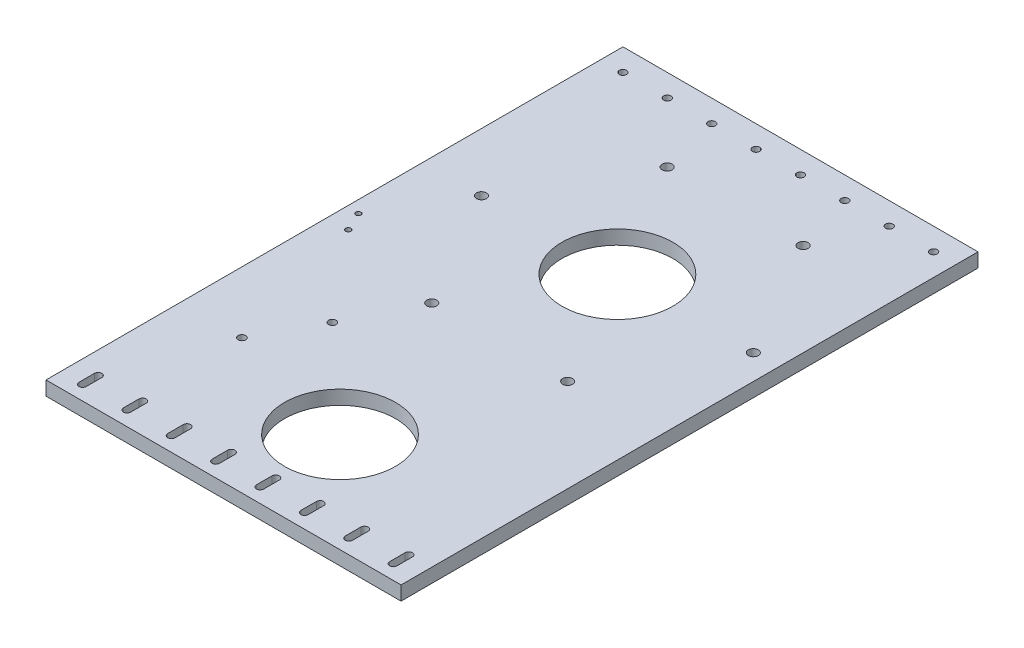
SolidWorks part; units mm, degrees
material "6061 Alloy"
ref_plane "Front Plane" through (0, 0, 0) normal (0, 0, 1) x (1, 0, 0)
ref_plane "Top Plane" through (0, 0, 0) normal (0, 1, 0) x (1, 0, 0)
ref_plane "Right Plane" through (0, 0, 0) normal (1, 0, 0) x (0, 0, -1)
sketch "Sketch1" plane through (0, 0, 0) normal (0, 1, 0) x (1, 0, 0)
  line L0 (87.5, 260) -> (87.5, 0) construction
  line L1 (0, 0) -> (160, 0)
  line L2 (0, 0) -> (0, 260)
  line L3 (0, 260) -> (160, 260)
  line L4 (160, 0) -> (160, 260)
  line L5 (87.5, 170) -> (148.75, 170) construction
  line L6 (10, 6.5) -> (10, 13.5) construction
  line L7 (5.4755, 135.2989) -> (9.5163, 126.7011) construction
  line L8 (22, 0) -> (22, 260) construction
  line L9 (22, 136) -> (0, 136) construction
  line L10 (22, 126) -> (0, 126) construction
  line L11 (0, 136) -> (0, 126) construction
  line L12 (17.3003, 136) -> (22, 126) construction
  line L13 (8.35, 6.5) -> (8.35, 13.5)
  line L14 (11.65, 6.5) -> (11.65, 13.5)
  line L15 (10, 250) -> (10, 0) construction
  line L16 (31.65, 6.5) -> (31.65, 13.5)
  line L17 (28.35, 6.5) -> (28.35, 13.5)
  line L18 (30, 6.5) -> (30, 13.5) construction
  line L19 (51.65, 6.5) -> (51.65, 13.5)
  line L20 (48.35, 6.5) -> (48.35, 13.5)
  line L21 (50, 6.5) -> (50, 13.5) construction
  line L22 (71.65, 6.5) -> (71.65, 13.5)
  line L23 (68.35, 6.5) -> (68.35, 13.5)
  line L24 (70, 6.5) -> (70, 13.5) construction
  line L25 (91.65, 6.5) -> (91.65, 13.5)
  line L26 (88.35, 6.5) -> (88.35, 13.5)
  line L27 (90, 6.5) -> (90, 13.5) construction
  line L28 (111.65, 6.5) -> (111.65, 13.5)
  line L29 (108.35, 6.5) -> (108.35, 13.5)
  line L30 (110, 6.5) -> (110, 13.5) construction
  line L31 (131.65, 6.5) -> (131.65, 13.5)
  line L32 (128.35, 6.5) -> (128.35, 13.5)
  line L33 (130, 6.5) -> (130, 13.5) construction
  line L34 (151.65, 6.5) -> (151.65, 13.5)
  line L35 (148.35, 6.5) -> (148.35, 13.5)
  line L36 (150, 6.5) -> (150, 13.5) construction
  line L37 (10, 250) -> (30, 250) construction
  circle A0 centre (87.5, 170) radius 25
  circle A1 centre (87.5, 45) radius 25
  circle A2 centre (87.5, 170) radius 61.25 construction
  circle A3 centre (148.75, 170) radius 2.25
  circle A4 centre (118.125, 116.9559) radius 2.25
  circle A5 centre (56.875, 116.9559) radius 2.25
  circle A6 centre (26.25, 170) radius 2.25
  circle A7 centre (56.875, 223.0441) radius 2.25
  circle A8 centre (118.125, 223.0441) radius 2.25
  circle A10 centre (5.4755, 135.2989) radius 1.175
  circle A11 centre (9.5163, 126.7011) radius 1.175
  circle A12 centre (87.5, 170) radius 78 construction
  circle A13 centre (10, 250) radius 1.65
  arc A14 (8.35, 6.5) -> (11.65, 6.5) centre (10, 6.5) ccw
  arc A15 (11.65, 13.5) -> (8.35, 13.5) centre (10, 13.5) ccw
  circle A16 centre (30, 250) radius 1.65
  arc A17 (28.35, 6.5) -> (31.65, 6.5) centre (30, 6.5) ccw
  arc A18 (31.65, 13.5) -> (28.35, 13.5) centre (30, 13.5) ccw
  circle A19 centre (50, 250) radius 1.65
  arc A20 (48.35, 6.5) -> (51.65, 6.5) centre (50, 6.5) ccw
  arc A21 (51.65, 13.5) -> (48.35, 13.5) centre (50, 13.5) ccw
  circle A22 centre (70, 250) radius 1.65
  arc A23 (68.35, 6.5) -> (71.65, 6.5) centre (70, 6.5) ccw
  arc A24 (71.65, 13.5) -> (68.35, 13.5) centre (70, 13.5) ccw
  circle A25 centre (90, 250) radius 1.65
  arc A26 (88.35, 6.5) -> (91.65, 6.5) centre (90, 6.5) ccw
  arc A27 (91.65, 13.5) -> (88.35, 13.5) centre (90, 13.5) ccw
  circle A28 centre (110, 250) radius 1.65
  arc A29 (108.35, 6.5) -> (111.65, 6.5) centre (110, 6.5) ccw
  arc A30 (111.65, 13.5) -> (108.35, 13.5) centre (110, 13.5) ccw
  circle A31 centre (130, 250) radius 1.65
  arc A32 (128.35, 6.5) -> (131.65, 6.5) centre (130, 6.5) ccw
  arc A33 (131.65, 13.5) -> (128.35, 13.5) centre (130, 13.5) ccw
  circle A34 centre (150, 250) radius 1.65
  arc A35 (148.35, 6.5) -> (151.65, 6.5) centre (150, 6.5) ccw
  arc A36 (151.65, 13.5) -> (148.35, 13.5) centre (150, 13.5) ccw
  point P15 (87.5, 170)
  point P29 (10, 10)
  point P42 (7.4959, 131)
  point P43 (0, 131)
  point P55 (30, 10)
  point P65 (50, 10)
  point P74 (70, 10)
  point P83 (90, 10)
  point P92 (110, 10)
  point P101 (130, 10)
  point P110 (150, 10)
  dimension "D3" = 50
  dimension "D4" = 50
  dimension "D7" = 122.5
  dimension "D8" = 4.5
  dimension "D11" = 124
  dimension "D13" = 2.35
  dimension "D16" = 156
  dimension "D19" = 3.3
  dimension "D24" = 240
  dimension "D1" = 160
  dimension "D2" = 260
  dimension "D5" = 125
  dimension "D6" = 90
  dimension "D10" = 61.25
  dimension "D12" = 65.5
  dimension "D14" = 9.5
  dimension "D15" = 10
  dimension "D17" = 11
  dimension "D18" = 72.5
  dimension "D20" = 10
  dimension "D21" = 10
  dimension "D22" = 3.3
  dimension "D23" = 7
  dimension "D26" = 20
  dimension "D25" = 8
  dimension "D9" = 6
extrude "Boss-Extrude1" add sketch "Sketch1" along normal blind 6.35 contours A1 | A0 | A4 | A8 | A7 | A6 | L4 L3 L2 L1 | A3 | A5 | A11 | A10 | A28 | A25 | A31 | A34 | A22 | A19 | A16 | A13 | L14 A15 L13 A14 | L16 A18 L17 A17 | L19 A21 L20 A20 | L22 A24 L23 A23 | L25 A27 L26 A26 | L28 A30 L29 A29 | L31 A33 L32 A32 | L34 A36 L35 A35 region at (87.5, 0, -170) region at (87.5, 0, -45) region at (118.125, 0, -116.9559) region at (26.25, 0, -170) region at (56.875, 0, -223.0441) region at (118.125, 0, -223.0441)
sketch "Sketch2" plane through (0, 6.35, 0) normal (0, 1, 0) x (1, 0, 0)
  line L0 (27.6639, 60.641) -> (42.0639, 86.959) construction
  line L1 (87.5, 170) -> (42.0639, 86.959) construction
  line L2 (34.8639, 73.8) -> (87.5, 45) construction
  circle A0 centre (27.6639, 60.641) radius 1.7
  circle A1 centre (42.0639, 86.959) radius 1.7
  dimension "D1" = 3.4
  dimension "D2" = 30
  dimension "D3" = 60
extrude "Cut-Extrude1" cut sketch "Sketch2" against normal through all
